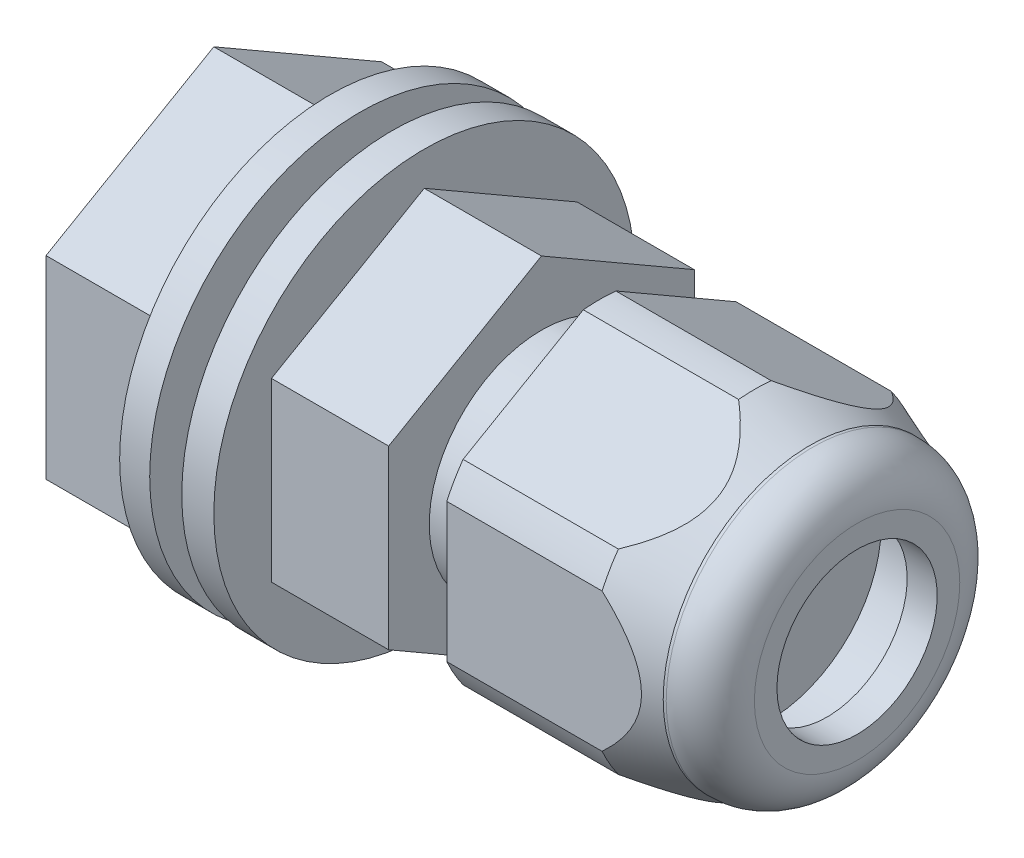
SolidWorks part; units mm, degrees
ref_plane "Front" through (0, 0, 0) normal (0, 0, 1) x (1, 0, 0)
ref_plane "Top" through (0, 0, 0) normal (0, 1, 0) x (1, 0, 0)
ref_plane "Right" through (0, 0, 0) normal (1, 0, 0) x (0, 0, -1)
sketch "Sketch1" plane through (0, 0, 0) normal (1, 0, 0) x (0, 0, -1)
  circle A0 centre (0, 0) radius 6.2
  dimension "\"c\"D1" = 12.4
extrude "Boss-Extrude1" add sketch "Sketch1" along normal blind 10.8
sketch "Sketch2" plane through (10.8, 0, 0) normal (1, 0, 0) x (0, 0, -1)
  line L1 (0, -8.8046) -> (7.625, -4.4023)
  line L2 (7.625, -4.4023) -> (7.625, 4.4023)
  line L3 (7.625, 4.4023) -> (0, 8.8046)
  line L4 (0, 8.8046) -> (-7.625, 4.4023)
  line L5 (-7.625, 4.4023) -> (-7.625, -4.4023)
  line L6 (-7.625, -4.4023) -> (0, -8.8046)
  circle A0 centre (0, 0) radius 7.625 construction
  dimension "\"hex\"D1" = 15.25
extrude "Boss-Extrude2" add sketch "Sketch2" along normal blind 5.85
sketch "Sketch3" plane through (16.65, 0, 0) normal (1, 0, 0) x (0, 0, -1)
  circle A0 centre (0, 0) radius 5.6
  dimension "\"body2\"D1" = 11.2
extrude "Boss-Extrude3" add sketch "Sketch3" along normal offset from surface (11.35 mm away) 28 up to face at (0, 0, -6.2)
sketch "Sketch4" plane through (10.8, 0, 0) normal (-1, 0, 0) x (0, 0, 1)
  circle A0 centre (0, 0) radius 10.5
  dimension "\"gasket diameter\"D1" = 21
extrude "Boss-Extrude4" add sketch "Sketch4" along normal blind 1.6
ref_plane "Plane1" through (7.6, 0, 0) normal (-1, 0, 0) x (0, 0, 1)
ref_axis "Axis1" through (7.6, 0, 11.55) along (0, 0, -1)
sketch "Sketch5" plane through (7.6, 0, 0) normal (-1, 0, 0) x (0, 0, 1)
  circle A0 centre (0, 0) radius 10.5
  dimension "\"H\"D1" = 21
extrude "Boss-Extrude5" add sketch "Sketch5" along normal blind 7.3
sketch "Sketch6" plane through (0.3, 0, 0) normal (-1, 0, 0) x (0, 0, 1)
  line L1 (0, -9.6706) -> (8.375, -4.8353)
  line L2 (8.375, -4.8353) -> (8.375, 4.8353)
  line L3 (8.375, 4.8353) -> (0, 9.6706)
  line L4 (0, 9.6706) -> (-8.375, 4.8353)
  line L5 (-8.375, 4.8353) -> (-8.375, -4.8353)
  line L6 (-8.375, -4.8353) -> (0, -9.6706)
  circle A0 centre (0, 0) radius 8.375 construction
  circle A1 centre (0, 0) radius 13.375
  dimension "\"NUT DIA\"D1" = 16.75
  dimension "D2" = 5
extrude "Cut-Extrude1" cut sketch "Sketch6" against normal offset from surface (5.8 mm away) 1.5 up to face at (7.6, 0, 10.5)
sketch "Sketch7" plane through (0, 0, 0) normal (-1, 0, 0) x (0, 0, 1)
  circle A0 centre (0, 0) radius 4
  dimension "\"B\"D1" = 8
extrude "Cut-Extrude2" cut sketch "Sketch7" against normal offset from surface (16.5 mm away) 11.5 up to face at (28, 0, -5.6)
sketch "Sketch8" plane through (28, 0, 0) normal (1, 0, 0) x (0, 0, -1)
  circle A0 centre (0, 0) radius 1.9
  dimension "\"A\"D1" = 3.8
extrude "Cut-Extrude3" cut sketch "Sketch8" against normal up to surface (11.5 mm away) up to face at (16.5, 0, -4)
sketch "Sketch9" plane through (0, 0, 0) normal (0, 0, 1) x (1, 0, 0)
  line L0 (19.55, 8.375) -> (27.3, 8.375)
  line L1 (27.3, 8.375) -> (30.05, 7.325)
  line L2 (30.05, 7.325) -> (30.2, 7.325)
  line L3 (32.4, 5.125) -> (32.4, 4)
  line L4 (19.55, 8.375) -> (19.55, 5.6)
  line L5 (28, 5.6) -> (16.65, 5.6) construction
  line L6 (19.55, 5.6) -> (30.425, 5.6)
  line L7 (30.9, 5.125) -> (30.9, 4)
  line L8 (30.9, 4) -> (32.4, 4)
  line L9 (0, 0) -> (59.2195, 0) construction
  line L11 (16.65, 4.4023) -> (16.65, 8.8046) construction
  arc A0 (32.4, 5.125) -> (30.2, 7.325) centre (30.2, 5.125) ccw
  arc A1 (30.9, 5.125) -> (30.425, 5.6) centre (30.425, 5.125) ccw
  dimension "D6" = 2.2
  dimension "\"OD COLLET\"D1" = 16.75
  dimension "\"C_LENGTH\"D2" = 15.75
  dimension "\"ID COLLET\"D3" = 8
  dimension "D4" = 10.5
  dimension "D5" = 2.9
  dimension "\"OD2\"D7" = 14.65
  dimension "D8" = 2.75
  dimension "D10" = 1.5
revolve "Revolve1" add sketch "Sketch9" angle 360 about L9
sketch "Sketch10" plane through (32.4, 0, 0) normal (1, 0, 0) x (0, 0, -1)
  line L1 (7.625, -4.4023) -> (7.625, 4.4023)
  line L2 (7.625, 4.4023) -> (0, 8.8046)
  line L3 (0, 8.8046) -> (-7.625, 4.4023)
  line L4 (-7.625, 4.4023) -> (-7.625, -4.4023)
  line L5 (-7.625, -4.4023) -> (0, -8.8046)
  line L6 (0, -8.8046) -> (7.625, -4.4023)
  circle A0 centre (0, 0) radius 7.625 construction
  circle A1 centre (0, 0) radius 12.625
  dimension "\"COLLET HEX\"D1" = 15.25
  dimension "D2" = 5
extrude "Cut-Extrude4" cut sketch "Sketch10" against normal up to surface (12.85 mm away) up to face at (19.55, 0, -5.6)
